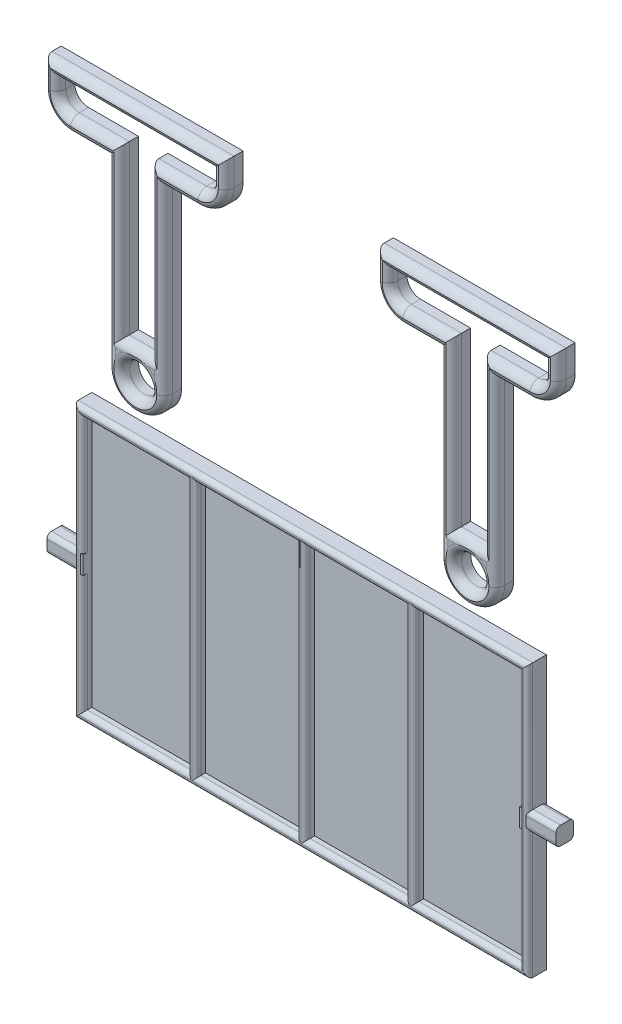
SolidWorks part; units mm, degrees
ref_plane "Alzado" through (0, 0, 0) normal (0, 0, 1) x (1, 0, 0)
ref_plane "Planta" through (0, 0, 0) normal (0, 1, 0) x (1, 0, 0)
ref_plane "Vista lateral" through (0, 0, 0) normal (1, 0, 0) x (0, 0, -1)
sketch "Croquis1" plane through (0, 0, 0) normal (0, 0, 1) x (1, 0, 0)
  line L1 (25, -15) -> (-25, -15)
  line L2 (25, -15) -> (25, 15)
  line L3 (25, 15) -> (-25, 15)
  line L4 (-25, -15) -> (-25, 15)
  line L5 (25, -15) -> (-25, 15) construction
  line L6 (25, 15) -> (-25, -15) construction
  point P0 (0, 0)
  dimension "D1" = 50
  dimension "D2" = 30
extrude "Saliente-Extruir1" add sketch "Croquis1" along normal blind 1
sketch "Croquis2" plane through (0, 0, 1) normal (0, 0, 1) x (1, 0, 0)
  line L0 (-25, -15) -> (25, -15) construction
  line L1 (-25, 15) -> (-24, 15)
  line L2 (-25, 15) -> (-25, -15)
  line L3 (-25, -15) -> (-24, -15)
  line L4 (-24, 14) -> (-24, -14)
  line L5 (25, -15) -> (25, 15) construction
  line L6 (-24, -15) -> (25, -15)
  line L8 (-24, -14) -> (-12.5, -14)
  line L9 (25, -15) -> (25, -14)
  line L10 (-0.5, -14) -> (-0.5, 14)
  line L11 (25, 15) -> (24, 15)
  line L12 (25, 15) -> (25, -14)
  line L14 (24, 14) -> (24, -14)
  line L15 (-24, 15) -> (24, 15)
  line L17 (-24, 14) -> (-12.5, 14)
  line L33 (0.5, -14) -> (0.5, 14)
  line L34 (0.5, 14) -> (11.5, 14)
  line L35 (12.5, 14) -> (24, 14)
  line L36 (12.5, -14) -> (24, -14)
  line L40 (12.5, -14) -> (12.5, 14)
  line L41 (11.5, -14) -> (11.5, 14)
  line L42 (-11.5, -14) -> (-0.5, -14)
  line L45 (0.5, -14) -> (11.5, -14)
  line L46 (-11.5, -14) -> (-11.5, 14)
  line L47 (-12.5, -14) -> (-12.5, 14)
  line L48 (-11.5, 14) -> (-0.5, 14)
  line L49 (0.5, -14) -> (0.5104, -14.2924) construction
  point P18 (12, 0)
  point P19 (0, 0)
  point P29 (-12, 0)
  dimension "D1" = 1
  dimension "D2" = 1
  dimension "D3" = 12
  dimension "D4" = 12
extrude "Saliente-Extruir2" add sketch "Croquis2" along normal blind 1
fillet "Redondeo1" radius 0.5 20 edges at (-6, 14, 2) (-11.5, 0, 2) (-6, -14, 2) (-0.5, 0, 2) (6, 14, 2) (0.5, 0, 2) (6, -14, 2) (11.5, 0, 2) (18.25, 14, 2) (12.5, 0, 2) (18.25, -14, 2) (24, 0, 2) (-18.25, 14, 2) (-24, 0, 2) (-18.25, -14, 2) (-12.5, 0, 2) (0, 15, 2) (25, 0, 2) (0, -15, 2) (-25, 0, 2)
sketch "Croquis3" plane through (0, 0, 1) normal (0, 0, 1) x (1, 0, 0)
  line L1 (-28, 1) -> (-24, 1)
  line L2 (-28, 1) -> (-28, -1)
  line L3 (-28, -1) -> (-24, -1)
  line L4 (-24, 1) -> (-24, -1)
  line L5 (0, 19.7296) -> (0, -19.5816) construction
  line L6 (24, 1) -> (24, -1)
  line L7 (-24, 14) -> (-24, -14) construction
  line L8 (28, -1) -> (24, -1)
  line L9 (28, 1) -> (28, -1)
  line L10 (28, 1) -> (24, 1)
  point P0 (-25, 0)
  point P14 (25, 0)
extrude "Saliente-Extruir3" add sketch "Croquis3" along normal blind 0.95 and the other way blind 1
fillet "Redondeo3" radius 0.5 8 edges at (-26.5, -1, 0) (-26.5, 1, 0) (-26.359, -1, 1.95) (-26.359, 1, 1.95) (26.5, -1, 0) (26.5, 1, 0) (26.359, -1, 1.95) (26.359, 1, 1.95)
sketch "Croquis4" plane through (0, 0, 0) normal (0, 0, 1) x (1, 0, 0)
  line L0 (15.1633, 40.3149) -> (11.1633, 40.3149)
  line L2 (21.4105, 20.3149) -> (21.4105, 40.3149)
  line L4 (15.1633, 20.3149) -> (15.1633, 40.3149)
  line L5 (25.1633, 40.3149) -> (21.4105, 40.3149)
  line L6 (28.1633, 43.3149) -> (28.1633, 46.3149)
  line L7 (28.1633, 46.3149) -> (8.1633, 46.3149)
  line L8 (8.1633, 43.3149) -> (8.1633, 46.3149)
  line L9 (16.6633, 41.9651) -> (11.1633, 41.9651)
  line L10 (19.9105, 23.5449) -> (16.6633, 23.5449)
  line L11 (19.9105, 23.5449) -> (19.9105, 41.9651)
  line L12 (19.9105, 44.8149) -> (16.6633, 44.8149)
  line L13 (16.6633, 23.5449) -> (16.6633, 41.9651)
  line L14 (26.6633, 44.8149) -> (9.6633, 44.8149)
  line L15 (26.6633, 44.8149) -> (26.6633, 43.4651)
  line L16 (25.1633, 41.9651) -> (19.9105, 41.9651)
  line L17 (9.6633, 44.8149) -> (9.6633, 43.4651)
  line L18 (-28.3736, 43.3149) -> (-28.3736, 46.3149)
  line L19 (-11.3736, 40.3149) -> (-15.1264, 40.3149)
  line L20 (-9.8736, 44.8149) -> (-9.8736, 43.4651)
  line L21 (-15.1264, 20.3149) -> (-15.1264, 40.3149)
  line L22 (-16.6264, 44.8149) -> (-19.8736, 44.8149)
  line L23 (-19.8736, 23.5449) -> (-19.8736, 41.9651)
  line L24 (-26.8736, 44.8149) -> (-26.8736, 43.4651)
  line L25 (-19.8736, 41.9651) -> (-25.3736, 41.9651)
  line L26 (-16.6264, 23.5449) -> (-19.8736, 23.5449)
  line L27 (-11.3736, 41.9651) -> (-16.6264, 41.9651)
  line L28 (-21.3736, 40.3149) -> (-25.3736, 40.3149)
  line L29 (-8.3736, 46.3149) -> (-28.3736, 46.3149)
  line L30 (-9.8736, 44.8149) -> (-26.8736, 44.8149)
  line L31 (-8.3736, 43.3149) -> (-8.3736, 46.3149)
  line L32 (-16.6264, 23.5449) -> (-16.6264, 41.9651)
  line L33 (-21.3736, 20.3149) -> (-21.3736, 40.3149)
  circle A0 centre (18.2869, 20.3149) radius 1.6
  arc A1 (15.1633, 20.3149) -> (21.4105, 20.3149) centre (18.2869, 20.3149) ccw
  arc A2 (11.1633, 40.3149) -> (8.1633, 43.3149) centre (11.1633, 43.3149) cw
  arc A3 (25.1633, 40.3149) -> (28.1633, 43.3149) centre (25.1633, 43.3149) ccw
  arc A4 (11.1633, 41.9651) -> (9.6633, 43.4651) centre (11.1633, 43.4651) cw
  arc A5 (26.6633, 43.4651) -> (25.1633, 41.9651) centre (25.1633, 43.4651) cw
  arc A6 (-21.3736, 20.3149) -> (-15.1264, 20.3149) centre (-18.25, 20.3149) ccw
  circle A7 centre (-18.25, 20.3149) radius 1.6
  arc A8 (-11.3736, 40.3149) -> (-8.3736, 43.3149) centre (-11.3736, 43.3149) ccw
  arc A9 (-25.3736, 41.9651) -> (-26.8736, 43.4651) centre (-25.3736, 43.4651) cw
  arc A10 (-25.3736, 40.3149) -> (-28.3736, 43.3149) centre (-25.3736, 43.3149) cw
  arc A11 (-9.8736, 43.4651) -> (-11.3736, 41.9651) centre (-11.3736, 43.4651) cw
  point P14 (18.2869, 30.7547)
  point P43 (-18.25, 30.7547)
  dimension "D1" = 3
  dimension "D5" = 1.5
  dimension "D6" = 3
  dimension "D10" = 1.5
  dimension "D2" = 1.5
  dimension "D3" = 1.5
  dimension "D4" = 1.5
  dimension "D7" = 1.5
  dimension "D8" = 1.5
  dimension "D9" = 1.5
extrude "Saliente-Extruir6" add sketch "Croquis4" along normal blind 2 separate body contours L2 L5 A3 L6 L7 L8 A2 L0 L4 A1 | L11 L16 A5 L15 L14 L17 A4 L9 L13 L10 | A0 | A7 | L23 L25 A9 L24 L30 L20 A11 L27 L32 L26 | L33 L28 A10 L18 L29 L31 A8 L19 L21 A6
fillet "Redondeo4" radius 1 21 edges at (19.8869, 20.3149, 2) (19.9105, 32.755, 2) (22.5369, 41.9651, 2) (26.224, 42.4045, 2) (26.6633, 44.14, 2) (18.1633, 44.8149, 2) (9.6633, 44.14, 2) (10.1027, 42.4045, 2) (13.9133, 41.9651, 2) (16.6633, 32.755, 2) (18.2869, 23.5449, 2) (15.1633, 30.3149, 2) (13.1633, 40.3149, 2) (9.042, 41.1936, 2) (8.1633, 44.8149, 2) (18.1633, 46.3149, 2) (28.1633, 44.8149, 2) (27.2847, 41.1936, 2) (23.2869, 40.3149, 2) (21.4105, 30.3149, 2) (18.2869, 17.1913, 2)
fillet "Redondeo5" radius 1 21 edges at (-16.65, 20.3149, 2) (-21.3736, 30.3149, 2) (-23.3736, 40.3149, 2) (-27.4949, 41.1936, 2) (-28.3736, 44.8149, 2) (-18.3736, 46.3149, 2) (-8.3736, 44.8149, 2) (-9.2523, 41.1936, 2) (-13.25, 40.3149, 2) (-15.1264, 30.3149, 2) (-18.25, 17.1913, 2) (-16.6264, 32.755, 2) (-14, 41.9651, 2) (-10.3129, 42.4045, 2) (-9.8736, 44.14, 2) (-18.3736, 44.8149, 2) (-26.8736, 44.14, 2) (-26.4343, 42.4045, 2) (-22.6236, 41.9651, 2) (-19.8736, 32.755, 2) (-18.25, 23.5449, 2)
